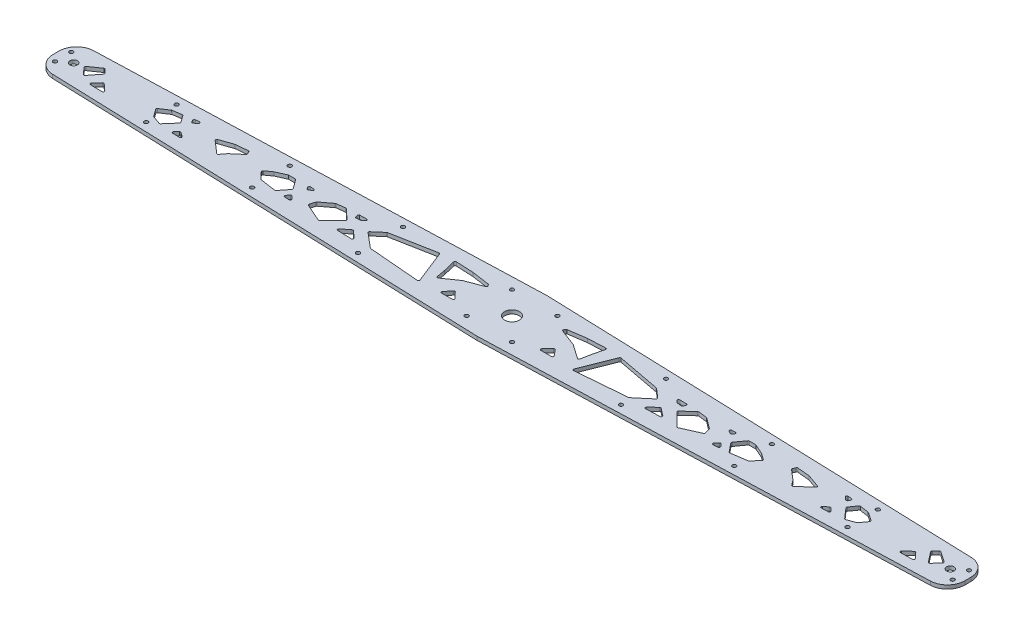
SolidWorks part; units mm, degrees
material "6061-T6 (SS)"
ref_plane "Front Plane" through (0, 0, 0) normal (0, 0, 1) x (1, 0, 0)
ref_plane "Top Plane" through (0, 0, 0) normal (0, 1, 0) x (1, 0, 0)
ref_plane "Right Plane" through (0, 0, 0) normal (1, 0, 0) x (0, 0, -1)
sketch "Sketch2" plane through (0, 0, 0) normal (0, 1, 0) x (1, 0, 0)
  line L0 (0, 0) -> (0, 30) construction
  line L1 (0, 0) -> (0, -30) construction
  line L2 (0, 0) -> (-375, 0) construction
  line L3 (-375, 17.5) -> (0, 30)
  line L4 (-375, -17.5) -> (0, -30)
  line L5 (375, -17.5) -> (0, -30)
  line L6 (375, 17.5) -> (0, 30)
  line L7 (-375, 17.5) -> (-375.4997, 17.4833)
  line L8 (-390, 2.4917) -> (-390, -2.4917)
  line L9 (-375.4997, -17.4833) -> (-375, -17.5)
  line L10 (-375, 17.5) -> (-375, -17.5) construction
  line L11 (390, 2.4917) -> (390, -2.4917)
  line L12 (375.4997, -17.4833) -> (375, -17.5)
  line L13 (375, 17.5) -> (375, -17.5) construction
  line L14 (375, 17.5) -> (375.4997, 17.4833)
  arc A2 (390, -2.4917) -> (375.4997, -17.4833) centre (375, -2.4917) cw
  arc A3 (390, 2.4917) -> (375.4997, 17.4833) centre (375, 2.4917) ccw
  arc A4 (-390, -2.4917) -> (-375.4997, -17.4833) centre (-375, -2.4917) ccw
  arc A5 (-375.4997, 17.4833) -> (-390, 2.4917) centre (-375, 2.4917) ccw
  point P15 (390, -17)
  point P18 (390, 17)
  point P21 (-390, -17)
  point P24 (-390, 17)
  point P26 (-390, 0)
  point P27 (390, 0)
  point P28 (375, 0)
  dimension "D4" = 15
  dimension "D1" = 60
  dimension "Half of Chassis Width" = 375
  dimension "FullLength" = 390
  dimension "D2" = 35
extrude "Boss-Extrude1" add sketch "Sketch2" along normal blind 3.18
sketch "Sketch3" plane through (0, 3.18, 0) normal (0, 1, 0) x (1, 0, 0)
  line L0 (0, 30) -> (0, -30) construction
  line L1 (-375, 0) -> (0, 0) construction
  line L2 (-390, 0) -> (-375, 0) construction
  line L3 (-206.25, 16.125) -> (-206.25, 0) construction
  line L4 (-112.5, -19.25) -> (-112.5, 0) construction
  line L5 (-390, 2.4917) -> (-390, -2.4917) construction
  line L6 (-375.4997, -17.4833) -> (0, -30) construction
  line L7 (-206.25, 16.125) -> (-206.25, 23.125) construction
  line L8 (0, 30) -> (-375.4997, 17.4833) construction
  line L9 (-112.5, -19.25) -> (-112.5, -26.25) construction
  line L10 (-375, 0) -> (-375, 17.5) construction
  line L11 (0, 30) -> (-375.4997, 17.4833) construction
  line L12 (-19.4207, 0) -> (-19.4207, 19.4207) construction
  line L13 (-19.4207, 19.4207) -> (0, 19.4207) construction
  line L14 (-300, 13) -> (-300, 0) construction
  line L15 (-300, 13) -> (-300, 20) construction
  line L16 (-19.4207, 19.4207) -> (-18.254, 18.254) construction
  line L17 (-18.254, 18.254) -> (-16.8397, 16.8397) construction
  line L18 (-16.8397, 16.8397) -> (0, 0) construction
  circle A0 centre (0, 0) radius 6.35
  circle A1 centre (-375, 0) radius 3.175
  circle A3 centre (-206.25, 16.125) radius 1.65
  circle A4 centre (-112.5, -19.25) radius 1.65
  circle A8 centre (375, 0) radius 3.175
  circle A9 centre (-112.5, 19.25) radius 1.65
  circle A10 centre (-206.25, -16.125) radius 1.65
  circle A11 centre (112.5, -19.25) radius 1.65
  circle A12 centre (112.5, 19.25) radius 1.65
  circle A13 centre (206.25, -16.125) radius 1.65
  circle A14 centre (206.25, 16.125) radius 1.65
  circle A15 centre (-384, 7) radius 1.65
  circle A16 centre (-384, -7) radius 1.65
  circle A17 centre (384, -7) radius 1.65
  circle A18 centre (384, 7) radius 1.65
  circle A19 centre (-19.4207, 19.4207) radius 1.65
  circle A20 centre (-19.4207, -19.4207) radius 1.65
  circle A21 centre (19.4207, -19.4207) radius 1.65
  circle A22 centre (19.4207, 19.4207) radius 1.65
  circle A23 centre (-300, 13) radius 1.65
  circle A25 centre (-300, -13) radius 1.65
  circle A26 centre (300, -13) radius 1.65
  circle A27 centre (300, 13) radius 1.65
  circle A28 centre (0, 0) radius 23.815 construction
  dimension "D1" = 12.7
  dimension "D2" = 6.35
  dimension "D3" = 3.3
  dimension "D11" = 47.63
  dimension "Hole2" = 206.25
  dimension "Hole1" = 112.5
  dimension "D5" = 7
  dimension "D6" = 7
  dimension "BallJointHoles" = 375
  dimension "D4" = 9
  dimension "D7" = 7
  dimension "D10" = 7
  dimension "Hole3" = 300
  dimension "D8" = 45
  dimension "D9" = 2
extrude "Cut-Extrude1" cut sketch "Sketch3" against normal through all
sketch "Sketch11" plane through (0, 3.18, 0) normal (0, 1, 0) x (1, 0, 0)
  line L0 (-46.9557, -13.2542) -> (-37.875, -13.2542)
  line L1 (-37.1556, -11.5596) -> (-42.0676, -6.4723)
  line L2 (-43.5604, -6.533) -> (-47.7292, -11.6204)
  line L3 (-59.5368, -3.5154) -> (-47.4685, 4.8982)
  line L4 (-47.2514, 5.0128) -> (-32.9145, 10.4523)
  line L5 (-32.4489, 11.9591) -> (-33.1525, 12.9684)
  line L6 (-33.8304, 13.3863) -> (-49.02, 15.572)
  line L7 (-49.1165, 15.5811) -> (-63.9426, 16.263)
  line L8 (-64.9605, 15.0288) -> (-62.5316, 4.9966)
  line L9 (-62.5198, 4.9409) -> (-61.0924, -2.8747)
  line L10 (-65.8675, -12.8511) -> (-76.8188, 14.811)
  line L11 (-77.9343, 15.4255) -> (-114.9795, 8.4218)
  line L12 (-115.4464, 8.1969) -> (-123.167, 1.5465)
  line L13 (-123.1594, 0.0246) -> (-110.8626, -10.3558)
  line L14 (-110.3008, -10.5882) -> (-66.8805, -14.2157)
  line L15 (-138.5004, -9.5121) -> (-132.2056, -4.6096)
  line L16 (-130.9112, -4.6653) -> (-125.244, -9.9207)
  line L17 (-125.9535, -11.6535) -> (-137.9154, -11.3006)
  line L18 (-139.7398, 9.4667) -> (-133.9309, 9.5926)
  line L19 (-133.2625, 7.8301) -> (-134.9958, 6.3603)
  line L20 (-135.5199, 6.1305) -> (-138.9791, 5.703)
  line L21 (-140.0462, 6.3668) -> (-140.6626, 8.1383)
  line L22 (-141.8691, 0.7038) -> (-150.2933, 8.5613)
  line L23 (-151.1009, 8.8221) -> (-158.4619, 7.8903)
  line L24 (-158.9389, 7.6963) -> (-167.8356, 0.9782)
  line L25 (-168.1907, 0.4679) -> (-169.5321, -3.9958)
  line L26 (-168.9782, -5.1984) -> (-153.8251, -11.8864)
  line L27 (-152.7118, -11.6762) -> (-141.8417, -0.7321)
  line L28 (-182.755, -5.2991) -> (-180.5794, -7.8233)
  line L29 (-181.4108, -9.4734) -> (-185.4398, -9.1746)
  line L30 (-186.1343, -7.5374) -> (-184.2809, -5.312)
  line L31 (-180.4874, 6.1292) -> (-178.3441, 7.4076)
  line L32 (-181.8711, 6.4975) -> (-182.6505, 7.8822)
  line L33 (-181.7428, 9.3721) -> (-178.82, 9.2658)
  line L34 (-193.789, -8.0414) -> (-187.8521, -0.5946)
  line L35 (-187.8243, 0.6157) -> (-193.4347, 8.3562)
  line L36 (-194.2443, 8.7693) -> (-199.7029, 8.7693)
  line L37 (-200.107, 8.6841) -> (-208.4203, 5.0118)
  line L38 (-208.603, 4.9067) -> (-213.9284, 1.0469)
  line L39 (-214.0726, -0.445) -> (-208.7568, -6.1417)
  line L40 (-208.1697, -6.449) -> (-194.715, -8.4076)
  line L41 (-256.6711, 4.7188) -> (-245.675, 8.5314)
  line L42 (-245.4438, 8.5819) -> (-235.1147, 9.5829)
  line L43 (-234.0978, 8.9786) -> (-233.1902, 6.8425)
  line L44 (-233.4614, 5.6908) -> (-241.6844, -1.3268)
  line L45 (-241.8289, -1.4791) -> (-245.1843, -5.8567)
  line L46 (-246.6345, -6.0026) -> (-257.0001, 3.0196)
  line L47 (-281.1371, -8.1537) -> (-278.8183, -5.8349)
  line L48 (-277.5355, -5.7243) -> (-273.9985, -8.2141)
  line L49 (-274.6033, -10.0313) -> (-280.4592, -9.8604)
  line L50 (-280.7239, 9.8026) -> (-277.4888, 10.1273)
  line L51 (-276.7474, 8.3652) -> (-279.1047, 6.3939)
  line L52 (-280.6287, 6.6905) -> (-281.5065, 8.3372)
  line L53 (-290.1682, 8.0252) -> (-297.7443, 6.8637)
  line L54 (-298.1467, 6.7077) -> (-305.2049, 2.0111)
  line L55 (-305.4627, 0.5946) -> (-301.1479, -5.4038)
  line L56 (-300.6722, -5.7617) -> (-293.6679, -8.2613)
  line L57 (-292.5783, -7.9769) -> (-285.1124, 0.5795)
  line L58 (-285.0527, 1.8189) -> (-289.2035, 7.6187)
  line L63 (-360.7214, -4.4562) -> (-353.8164, 4.2927)
  line L64 (-353.8724, 5.5968) -> (-356.7795, 8.6925)
  line L65 (-358.0768, 8.8307) -> (-367.0377, 2.6417)
  line L66 (-367.221, 1.1593) -> (-362.258, -4.4963)
  line L67 (-352.3728, -7.3942) -> (-347.9195, -2.4852)
  line L68 (-346.5069, -2.4165) -> (-340.9196, -7.4852)
  line L69 (-341.6074, -9.2257) -> (-351.6481, -9.066)
  line L70 (0, 30) -> (0, -30) construction
  line L71 (37.1556, -11.5596) -> (42.0676, -6.4723)
  line L72 (46.9557, -13.2542) -> (37.875, -13.2542)
  line L73 (43.5604, -6.533) -> (47.7292, -11.6204)
  line L74 (64.9605, 15.0288) -> (62.5316, 4.9966)
  line L75 (49.1165, 15.5811) -> (63.9426, 16.263)
  line L76 (33.8304, 13.3863) -> (49.02, 15.572)
  line L77 (32.4489, 11.9591) -> (33.1525, 12.9684)
  line L78 (47.2514, 5.0128) -> (32.9145, 10.4523)
  line L79 (59.5368, -3.5154) -> (47.4685, 4.8982)
  line L80 (62.5198, 4.9409) -> (61.0924, -2.8747)
  line L81 (123.1594, 0.0246) -> (110.8626, -10.3558)
  line L82 (115.4464, 8.1969) -> (123.167, 1.5465)
  line L83 (77.9343, 15.4255) -> (114.9795, 8.4218)
  line L84 (65.8675, -12.8511) -> (76.8188, 14.811)
  line L85 (110.3008, -10.5882) -> (66.8805, -14.2157)
  line L86 (135.5199, 6.1305) -> (138.9791, 5.703)
  line L87 (133.2625, 7.8301) -> (134.9958, 6.3603)
  line L88 (139.7398, 9.4667) -> (133.9309, 9.5926)
  line L89 (140.0462, 6.3668) -> (140.6626, 8.1383)
  line L90 (130.9112, -4.6653) -> (125.244, -9.9207)
  line L91 (138.5004, -9.5121) -> (132.2056, -4.6096)
  line L92 (125.9535, -11.6535) -> (137.9154, -11.3006)
  line L93 (168.9782, -5.1984) -> (153.8251, -11.8864)
  line L94 (168.1907, 0.4679) -> (169.5321, -3.9958)
  line L95 (158.9389, 7.6963) -> (167.8356, 0.9782)
  line L96 (151.1009, 8.8221) -> (158.4619, 7.8903)
  line L97 (141.8691, 0.7038) -> (150.2933, 8.5613)
  line L98 (152.7118, -11.6762) -> (141.8417, -0.7321)
  line L99 (181.8711, 6.4975) -> (182.6505, 7.8822)
  line L100 (180.4874, 6.1292) -> (178.3441, 7.4076)
  line L101 (181.7428, 9.3721) -> (178.82, 9.2658)
  line L102 (181.4108, -9.4734) -> (185.4398, -9.1746)
  line L103 (182.755, -5.2991) -> (180.5794, -7.8233)
  line L104 (186.1343, -7.5374) -> (184.2809, -5.312)
  line L105 (214.0726, -0.445) -> (208.7568, -6.1417)
  line L106 (208.603, 4.9067) -> (213.9284, 1.0469)
  line L107 (200.107, 8.6841) -> (208.4203, 5.0118)
  line L108 (194.2443, 8.7693) -> (199.7029, 8.7693)
  line L109 (187.8243, 0.6157) -> (193.4347, 8.3562)
  line L110 (193.789, -8.0414) -> (187.8521, -0.5946)
  line L111 (208.1697, -6.449) -> (194.715, -8.4076)
  line L112 (241.8289, -1.4791) -> (245.1843, -5.8567)
  line L113 (233.4614, 5.6908) -> (241.6844, -1.3268)
  line L114 (234.0978, 8.9786) -> (233.1902, 6.8425)
  line L115 (245.4438, 8.5819) -> (235.1147, 9.5829)
  line L116 (256.6711, 4.7188) -> (245.675, 8.5314)
  line L117 (246.6345, -6.0026) -> (257.0001, 3.0196)
  line L118 (276.7474, 8.3652) -> (279.1047, 6.3939)
  line L119 (280.7239, 9.8026) -> (277.4888, 10.1273)
  line L120 (280.6287, 6.6905) -> (281.5065, 8.3372)
  line L123 (277.5355, -5.7243) -> (273.9985, -8.2141)
  line L124 (281.1371, -8.1537) -> (278.8183, -5.8349)
  line L125 (274.6033, -10.0313) -> (280.4592, -9.8604)
  line L126 (292.5783, -7.9769) -> (285.1124, 0.5795)
  line L127 (300.6722, -5.7617) -> (293.6679, -8.2613)
  line L128 (305.4627, 0.5946) -> (301.1479, -5.4038)
  line L129 (298.1467, 6.7077) -> (305.2049, 2.0111)
  line L130 (290.1682, 8.0252) -> (297.7443, 6.8637)
  line L131 (285.0527, 1.8189) -> (289.2035, 7.6187)
  line L132 (358.0768, 8.8307) -> (367.0377, 2.6417)
  line L133 (353.8724, 5.5968) -> (356.7795, 8.6925)
  line L134 (360.7214, -4.4562) -> (353.8164, 4.2927)
  line L135 (367.221, 1.1593) -> (362.258, -4.4963)
  line L136 (346.5069, -2.4165) -> (340.9196, -7.4852)
  line L137 (352.3728, -7.3942) -> (347.9195, -2.4852)
  line L138 (341.6074, -9.2257) -> (351.6481, -9.066)
  arc A8 (-245.1843, -5.8567) -> (-246.6345, -6.0026) centre (-245.978, -5.2484) cw
  arc A9 (-241.6844, -1.3268) -> (-241.8289, -1.4791) centre (-241.0352, -2.0874) ccw
  arc A10 (-233.1902, 6.8425) -> (-233.4614, 5.6908) centre (-234.1106, 6.4514) cw
  arc A11 (-235.1147, 9.5829) -> (-234.0978, 8.9786) centre (-235.0182, 8.5876) cw
  arc A12 (-245.675, 8.5314) -> (-245.4438, 8.5819) centre (-245.3474, 7.5866) cw
  arc A13 (-256.6711, 4.7188) -> (-257.0001, 3.0196) centre (-256.3435, 3.7739) ccw
  arc A14 (-277.4888, 10.1273) -> (-276.7474, 8.3652) centre (-277.3889, 9.1323) cw
  arc A15 (-280.7239, 9.8026) -> (-281.5065, 8.3372) centre (-280.6241, 8.8076) ccw
  arc A16 (-279.1047, 6.3939) -> (-280.6287, 6.6905) centre (-279.7462, 7.161) cw
  arc A17 (-273.9985, -8.2141) -> (-274.6033, -10.0313) centre (-274.5742, -9.0318) cw
  arc A18 (-281.1371, -8.1537) -> (-280.4592, -9.8604) centre (-280.43, -8.8608) ccw
  arc A19 (-278.8183, -5.8349) -> (-277.5355, -5.7243) centre (-278.1112, -6.542) cw
  arc A20 (-301.1479, -5.4038) -> (-300.6722, -5.7617) centre (-300.3361, -4.8199) ccw
  arc A21 (-305.2049, 2.0111) -> (-305.4627, 0.5946) centre (-304.6509, 1.1785) ccw
  arc A22 (-297.7443, 6.8637) -> (-298.1467, 6.7077) centre (-297.5928, 5.8752) ccw
  arc A23 (-290.1682, 8.0252) -> (-289.2035, 7.6187) centre (-290.0167, 7.0367) cw
  arc A24 (-285.1124, 0.5795) -> (-285.0527, 1.8189) centre (-285.8659, 1.2369) ccw
  arc A25 (-293.6679, -8.2613) -> (-292.5783, -7.9769) centre (-293.3318, -7.3195) ccw
  arc A26 (-340.9196, -7.4852) -> (-341.6074, -9.2257) centre (-341.5915, -8.2258) cw
  arc A27 (-352.3728, -7.3942) -> (-351.6481, -9.066) centre (-351.6322, -8.0661) ccw
  arc A28 (-347.9195, -2.4852) -> (-346.5069, -2.4165) centre (-347.1788, -3.1571) cw
  arc A29 (-353.8164, 4.2927) -> (-353.8724, 5.5968) centre (-354.6014, 4.9123) ccw
  arc A30 (-360.7214, -4.4562) -> (-362.258, -4.4963) centre (-361.5064, -3.8367) cw
  arc A31 (-367.0377, 2.6417) -> (-367.221, 1.1593) centre (-366.4694, 1.8189) ccw
  arc A32 (-356.7795, 8.6925) -> (-358.0768, 8.8307) centre (-357.5085, 8.0079) ccw
  arc A33 (-37.875, -13.2542) -> (-37.1556, -11.5596) centre (-37.875, -12.2542) ccw
  arc A34 (-46.9557, -13.2542) -> (-47.7292, -11.6204) centre (-46.9557, -12.2542) cw
  arc A35 (-42.0676, -6.4723) -> (-43.5604, -6.533) centre (-42.787, -7.1669) ccw
  arc A36 (-32.9145, 10.4523) -> (-32.4489, 11.9591) centre (-33.2692, 11.3872) ccw
  arc A37 (-33.1525, 12.9684) -> (-33.8304, 13.3863) centre (-33.9728, 12.3965) ccw
  arc A38 (-49.02, 15.572) -> (-49.1165, 15.5811) centre (-49.1625, 14.5822) ccw
  arc A39 (-47.4685, 4.8982) -> (-47.2514, 5.0128) centre (-46.8967, 4.0778) cw
  arc A40 (-62.5316, 4.9966) -> (-62.5198, 4.9409) centre (-63.5035, 4.7613) cw
  arc A41 (-59.5368, -3.5154) -> (-61.0924, -2.8747) centre (-60.1087, -2.695) cw
  arc A42 (-63.9426, 16.263) -> (-64.9605, 15.0288) centre (-63.9885, 15.2641) ccw
  arc A43 (-76.8188, 14.811) -> (-77.9343, 15.4255) centre (-77.7486, 14.4429) ccw
  arc A44 (-65.8675, -12.8511) -> (-66.8805, -14.2157) centre (-66.7973, -13.2192) cw
  arc A45 (-110.8626, -10.3558) -> (-110.3008, -10.5882) centre (-110.2175, -9.5917) ccw
  arc A46 (-114.9795, 8.4218) -> (-115.4464, 8.1969) centre (-114.7937, 7.4393) ccw
  arc A47 (-123.167, 1.5465) -> (-123.1594, 0.0246) centre (-122.5144, 0.7888) ccw
  arc A48 (-138.5004, -9.5121) -> (-137.9154, -11.3006) centre (-137.8859, -10.301) ccw
  arc A49 (-125.244, -9.9207) -> (-125.9535, -11.6535) centre (-125.924, -10.654) cw
  arc A50 (-132.2056, -4.6096) -> (-130.9112, -4.6653) centre (-131.5912, -5.3986) cw
  arc A51 (-138.9791, 5.703) -> (-140.0462, 6.3668) centre (-139.1017, 6.6954) cw
  arc A52 (-134.9958, 6.3603) -> (-135.5199, 6.1305) centre (-135.6426, 7.123) cw
  arc A53 (-133.9309, 9.5926) -> (-133.2625, 7.8301) centre (-133.9092, 8.5928) cw
  arc A54 (-139.7398, 9.4667) -> (-140.6626, 8.1383) centre (-139.7182, 8.4669) ccw
  arc A55 (-169.5321, -3.9958) -> (-168.9782, -5.1984) centre (-168.5744, -4.2836) ccw
  arc A56 (-167.8356, 0.9782) -> (-168.1907, 0.4679) centre (-167.233, 0.1801) ccw
  arc A57 (-158.4619, 7.8903) -> (-158.9389, 7.6963) centre (-158.3363, 6.8983) ccw
  arc A58 (-150.2933, 8.5613) -> (-151.1009, 8.8221) centre (-150.9754, 7.83) ccw
  arc A59 (-141.8691, 0.7038) -> (-141.8417, -0.7321) centre (-142.5512, -0.0274) cw
  arc A60 (-153.8251, -11.8864) -> (-152.7118, -11.6762) centre (-153.4213, -10.9715) ccw
  arc A61 (-180.4874, 6.1292) -> (-181.8711, 6.4975) centre (-180.9997, 6.988) cw
  arc A62 (-182.6505, 7.8822) -> (-181.7428, 9.3721) centre (-181.7791, 8.3727) cw
  arc A63 (-178.3441, 7.4076) -> (-178.82, 9.2658) centre (-178.8564, 8.2665) ccw
  arc A64 (-185.4398, -9.1746) -> (-186.1343, -7.5374) centre (-185.3659, -8.1773) cw
  arc A65 (-180.5794, -7.8233) -> (-181.4108, -9.4734) centre (-181.3369, -8.4762) cw
  arc A66 (-182.755, -5.2991) -> (-184.2809, -5.312) centre (-183.5125, -5.9519) ccw
  arc A67 (-208.4203, 5.0118) -> (-208.603, 4.9067) centre (-208.0162, 4.097) ccw
  arc A68 (-213.9284, 1.0469) -> (-214.0726, -0.445) centre (-213.3415, 0.2372) ccw
  arc A69 (-208.7568, -6.1417) -> (-208.1697, -6.449) centre (-208.0257, -5.4594) ccw
  arc A70 (-193.789, -8.0414) -> (-194.715, -8.4076) centre (-194.571, -7.418) cw
  arc A71 (-187.8521, -0.5946) -> (-187.8243, 0.6157) centre (-188.634, 0.0288) ccw
  arc A72 (-193.4347, 8.3562) -> (-194.2443, 8.7693) centre (-194.2443, 7.7693) ccw
  arc A73 (-199.7029, 8.7693) -> (-200.107, 8.6841) centre (-199.7029, 7.7693) ccw
  arc A74 (37.875, -13.2542) -> (37.1556, -11.5596) centre (37.875, -12.2542) cw
  arc A75 (46.9557, -13.2542) -> (47.7292, -11.6204) centre (46.9557, -12.2542) ccw
  arc A76 (42.0676, -6.4723) -> (43.5604, -6.533) centre (42.787, -7.1669) cw
  arc A77 (63.9426, 16.263) -> (64.9605, 15.0288) centre (63.9885, 15.2641) cw
  arc A78 (49.02, 15.572) -> (49.1165, 15.5811) centre (49.1625, 14.5822) cw
  arc A79 (33.1525, 12.9684) -> (33.8304, 13.3863) centre (33.9728, 12.3965) cw
  arc A80 (32.9145, 10.4523) -> (32.4489, 11.9591) centre (33.2692, 11.3872) cw
  arc A81 (47.4685, 4.8982) -> (47.2514, 5.0128) centre (46.8967, 4.0778) ccw
  arc A82 (62.5316, 4.9966) -> (62.5198, 4.9409) centre (63.5035, 4.7613) ccw
  arc A83 (59.5368, -3.5154) -> (61.0924, -2.8747) centre (60.1087, -2.695) ccw
  arc A84 (123.167, 1.5465) -> (123.1594, 0.0246) centre (122.5144, 0.7888) cw
  arc A85 (114.9795, 8.4218) -> (115.4464, 8.1969) centre (114.7937, 7.4393) cw
  arc A86 (76.8188, 14.811) -> (77.9343, 15.4255) centre (77.7486, 14.4429) cw
  arc A87 (65.8675, -12.8511) -> (66.8805, -14.2157) centre (66.7973, -13.2192) ccw
  arc A88 (110.8626, -10.3558) -> (110.3008, -10.5882) centre (110.2175, -9.5917) cw
  arc A89 (134.9958, 6.3603) -> (135.5199, 6.1305) centre (135.6426, 7.123) ccw
  arc A90 (133.9309, 9.5926) -> (133.2625, 7.8301) centre (133.9092, 8.5928) ccw
  arc A91 (138.9791, 5.703) -> (140.0462, 6.3668) centre (139.1017, 6.6954) ccw
  arc A92 (139.7398, 9.4667) -> (140.6626, 8.1383) centre (139.7182, 8.4669) cw
  arc A93 (132.2056, -4.6096) -> (130.9112, -4.6653) centre (131.5912, -5.3986) ccw
  arc A94 (138.5004, -9.5121) -> (137.9154, -11.3006) centre (137.8859, -10.301) cw
  arc A95 (125.244, -9.9207) -> (125.9535, -11.6535) centre (125.924, -10.654) ccw
  arc A96 (169.5321, -3.9958) -> (168.9782, -5.1984) centre (168.5744, -4.2836) cw
  arc A97 (167.8356, 0.9782) -> (168.1907, 0.4679) centre (167.233, 0.1801) cw
  arc A98 (158.4619, 7.8903) -> (158.9389, 7.6963) centre (158.3363, 6.8983) cw
  arc A99 (150.2933, 8.5613) -> (151.1009, 8.8221) centre (150.9754, 7.83) cw
  arc A100 (141.8691, 0.7038) -> (141.8417, -0.7321) centre (142.5512, -0.0274) ccw
  arc A101 (153.8251, -11.8864) -> (152.7118, -11.6762) centre (153.4213, -10.9715) cw
  arc A102 (180.4874, 6.1292) -> (181.8711, 6.4975) centre (180.9997, 6.988) ccw
  arc A103 (182.6505, 7.8822) -> (181.7428, 9.3721) centre (181.7791, 8.3727) ccw
  arc A104 (178.3441, 7.4076) -> (178.82, 9.2658) centre (178.8564, 8.2665) cw
  arc A105 (180.5794, -7.8233) -> (181.4108, -9.4734) centre (181.3369, -8.4762) ccw
  arc A106 (185.4398, -9.1746) -> (186.1343, -7.5374) centre (185.3659, -8.1773) ccw
  arc A107 (182.755, -5.2991) -> (184.2809, -5.312) centre (183.5125, -5.9519) cw
  arc A108 (213.9284, 1.0469) -> (214.0726, -0.445) centre (213.3415, 0.2372) cw
  arc A109 (208.4203, 5.0118) -> (208.603, 4.9067) centre (208.0162, 4.097) cw
  arc A110 (199.7029, 8.7693) -> (200.107, 8.6841) centre (199.7029, 7.7693) cw
  arc A111 (193.4347, 8.3562) -> (194.2443, 8.7693) centre (194.2443, 7.7693) cw
  arc A112 (187.8521, -0.5946) -> (187.8243, 0.6157) centre (188.634, 0.0288) cw
  arc A113 (208.7568, -6.1417) -> (208.1697, -6.449) centre (208.0257, -5.4594) cw
  arc A114 (193.789, -8.0414) -> (194.715, -8.4076) centre (194.571, -7.418) ccw
  arc A115 (241.6844, -1.3268) -> (241.8289, -1.4791) centre (241.0352, -2.0874) cw
  arc A116 (233.1902, 6.8425) -> (233.4614, 5.6908) centre (234.1106, 6.4514) ccw
  arc A117 (235.1147, 9.5829) -> (234.0978, 8.9786) centre (235.0182, 8.5876) ccw
  arc A118 (245.675, 8.5314) -> (245.4438, 8.5819) centre (245.3474, 7.5866) ccw
  arc A119 (245.1843, -5.8567) -> (246.6345, -6.0026) centre (245.978, -5.2484) ccw
  arc A120 (256.6711, 4.7188) -> (257.0001, 3.0196) centre (256.3435, 3.7739) cw
  arc A121 (277.4888, 10.1273) -> (276.7474, 8.3652) centre (277.3889, 9.1323) ccw
  arc A122 (280.7239, 9.8026) -> (281.5065, 8.3372) centre (280.6241, 8.8076) cw
  arc A123 (279.1047, 6.3939) -> (280.6287, 6.6905) centre (279.7462, 7.161) ccw
  arc A130 (278.8183, -5.8349) -> (277.5355, -5.7243) centre (278.1112, -6.542) ccw
  arc A131 (273.9985, -8.2141) -> (274.6033, -10.0313) centre (274.5742, -9.0318) ccw
  arc A132 (281.1371, -8.1537) -> (280.4592, -9.8604) centre (280.43, -8.8608) cw
  arc A133 (293.6679, -8.2613) -> (292.5783, -7.9769) centre (293.3318, -7.3195) cw
  arc A134 (301.1479, -5.4038) -> (300.6722, -5.7617) centre (300.3361, -4.8199) cw
  arc A135 (305.2049, 2.0111) -> (305.4627, 0.5946) centre (304.6509, 1.1785) cw
  arc A136 (297.7443, 6.8637) -> (298.1467, 6.7077) centre (297.5928, 5.8752) cw
  arc A137 (290.1682, 8.0252) -> (289.2035, 7.6187) centre (290.0167, 7.0367) ccw
  arc A138 (285.1124, 0.5795) -> (285.0527, 1.8189) centre (285.8659, 1.2369) cw
  arc A139 (356.7795, 8.6925) -> (358.0768, 8.8307) centre (357.5085, 8.0079) cw
  arc A140 (353.8164, 4.2927) -> (353.8724, 5.5968) centre (354.6014, 4.9123) cw
  arc A141 (360.7214, -4.4562) -> (362.258, -4.4963) centre (361.5064, -3.8367) ccw
  arc A142 (367.0377, 2.6417) -> (367.221, 1.1593) centre (366.4694, 1.8189) cw
  arc A143 (347.9195, -2.4852) -> (346.5069, -2.4165) centre (347.1788, -3.1571) ccw
  arc A144 (340.9196, -7.4852) -> (341.6074, -9.2257) centre (341.5915, -8.2258) ccw
  arc A145 (352.3728, -7.3942) -> (351.6481, -9.066) centre (351.6322, -8.0661) cw
  dimension "D5" = 1
  dimension "D6" = 1
  dimension "D7" = 1
  dimension "D8" = 1
  dimension "D9" = 1
  dimension "D10" = 1
  dimension "D11" = 1
  dimension "D12" = 1
  dimension "D13" = 1
  dimension "D14" = 1
  dimension "D15" = 1
  dimension "D16" = 1
  dimension "D17" = 1
  dimension "D18" = 1
  dimension "D19" = 1
  dimension "D20" = 1
  dimension "D21" = 1
  dimension "D22" = 1
  dimension "D23" = 1
  dimension "D24" = 1
  dimension "D25" = 1
  dimension "D26" = 1
  dimension "D27" = 1
  dimension "D28" = 1
  dimension "D29" = 1
  dimension "D30" = 1
  dimension "D31" = 1
  dimension "D32" = 1
  dimension "D33" = 1
  dimension "D34" = 1
  dimension "D35" = 1
  dimension "D36" = 1
  dimension "D37" = 1
  dimension "D38" = 1
  dimension "D39" = 1
  dimension "D40" = 1
  dimension "D41" = 1
  dimension "D42" = 1
  dimension "D43" = 1
  dimension "D44" = 1
  dimension "D45" = 1
  dimension "D46" = 1
  dimension "D47" = 1
  dimension "D48" = 1
  dimension "D49" = 1
  dimension "D50" = 1
  dimension "D51" = 1
  dimension "D52" = 1
  dimension "D53" = 1
  dimension "D54" = 1
  dimension "D55" = 1
  dimension "D56" = 1
  dimension "D57" = 1
  dimension "D58" = 1
  dimension "D59" = 1
  dimension "D60" = 1
  dimension "D61" = 1
  dimension "D62" = 1
  dimension "D63" = 1
  dimension "D64" = 1
  dimension "D65" = 1
  dimension "D66" = 1
  dimension "D67" = 1
  dimension "D68" = 1
  dimension "D69" = 1
  dimension "D70" = 1
extrude "Cut-Extrude8" cut sketch "Sketch11" against normal through all
equation "\"Hole2@Sketch3\"= \"Chassis Width@Differential System Assy - Option 1.Assembly\" / 2 * 0.55"
equation "\"Hole1@Sketch3\" = \"Chassis Width@Differential System Assy - Option 1.Assembly\" / 2 * 0.3"
equation "\"Half of Chassis Width@Sketch2\"= \"Chassis Width@Differential System Assy - Option 1.Assembly\" / 2"
equation "\"FullLength@Sketch2\"= \"Chassis Width@Differential System Assy - Option 1.Assembly\" / 2 * 1.04"
equation "\"BallJointHoles@Sketch3\"= \"Chassis Width@Differential System Assy - Option 1.Assembly\" / 2"
equation "\"Hole3@Sketch3\"= \"Chassis Width@Differential System Assy - Option 1.Assembly\" / 2 * 0.8"
